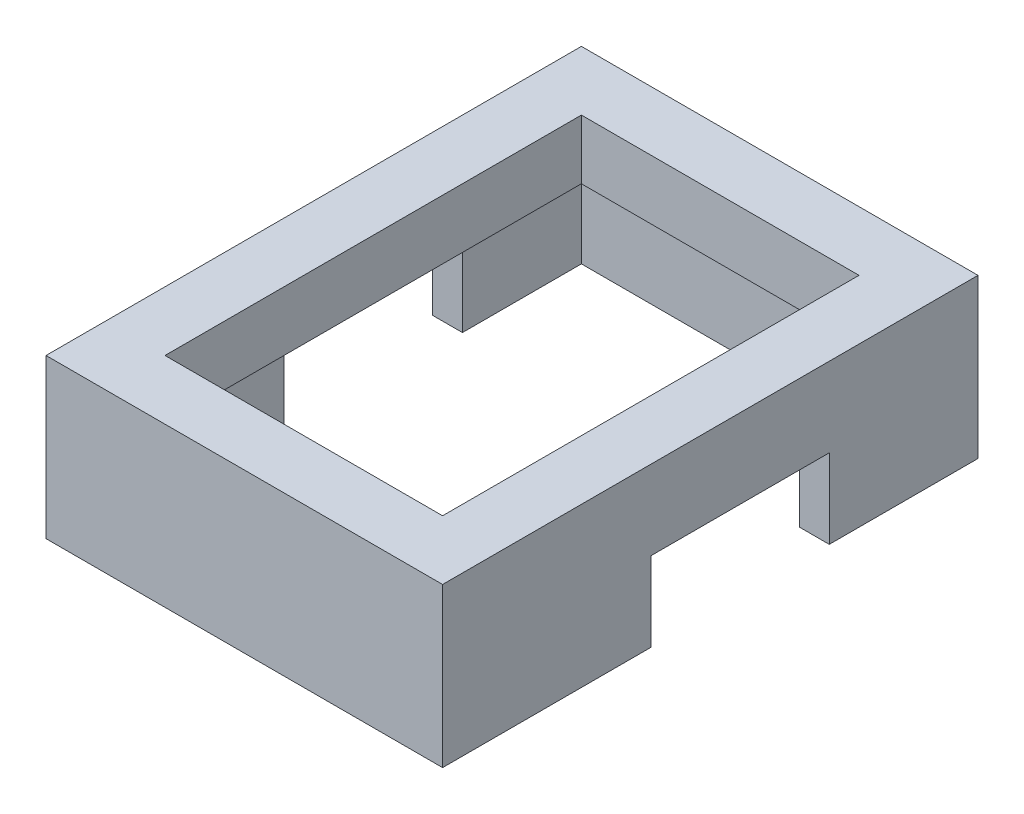
SolidWorks part; units mm, degrees
ref_plane "Front Plane" through (0, 0, 0) normal (0, 0, 1) x (1, 0, 0)
ref_plane "Top Plane" through (0, 0, 0) normal (0, 1, 0) x (1, 0, 0)
ref_plane "Right Plane" through (0, 0, 0) normal (1, 0, 0) x (0, 0, -1)
sketch "Sketch1" plane through (0, 0, 0) normal (0, 1, 0) x (1, 0, 0)
  line L1 (-20.9032, 9.871) -> (-0.9032, 9.871)
  line L2 (-20.9032, 9.871) -> (-20.9032, -17.129)
  line L3 (-20.9032, -17.129) -> (-0.9032, -17.129)
  line L4 (-0.9032, 9.871) -> (-0.9032, -17.129)
  dimension "D1" = 20
  dimension "D2" = 27
extrude "Boss-Extrude1" add sketch "Sketch1" along normal blind 8
sketch "Sketch2" plane through (-20.9032, 0, 0) normal (-1, 0, 0) x (0, 0, 1)
  line L0 (-9.871, 0) -> (17.129, 0) construction
  line L1 (-2.371, 4) -> (6.629, 4)
  line L2 (-2.371, 4) -> (-2.371, 0)
  line L3 (-2.371, 0) -> (6.629, 0)
  line L4 (6.629, 4) -> (6.629, 0)
  line L5 (-9.871, 8) -> (-9.871, 0) construction
  dimension "D1" = 9
  dimension "D2" = 4
  dimension "D3" = 7.5
extrude "Cut-Extrude1" cut sketch "Sketch2" against normal blind 20
sketch "Sketch3" plane through (0, 0, 0) normal (0, -1, 0) x (1, 0, 0)
  line L0 (-0.9032, -2.371) -> (-0.9032, -9.871) construction
  line L1 (-2.4032, -8.371) -> (-19.4032, -8.371)
  line L2 (-2.4032, -8.371) -> (-2.4032, 15.629)
  line L3 (-2.4032, 15.629) -> (-19.4032, 15.629)
  line L4 (-19.4032, -8.371) -> (-19.4032, 15.629)
  line L5 (-20.9032, -9.871) -> (-20.9032, -2.371) construction
  line L6 (-0.9032, -9.871) -> (-20.9032, -9.871) construction
  line L7 (-20.9032, 17.129) -> (-0.9032, 17.129) construction
  dimension "D1" = 1.5
  dimension "D2" = 1.5
  dimension "D3" = 1.5
  dimension "D4" = 1.5
extrude "Cut-Extrude2" cut sketch "Sketch3" against normal blind 5
sketch "Sketch4" plane through (0, 8, 0) normal (0, 1, 0) x (1, 0, 0)
  line L0 (-20.9032, 9.871) -> (-20.9032, -17.129) construction
  line L1 (-17.9032, 6.871) -> (-3.9032, 6.871)
  line L2 (-17.9032, 6.871) -> (-17.9032, -14.129)
  line L3 (-17.9032, -14.129) -> (-3.9032, -14.129)
  line L4 (-3.9032, 6.871) -> (-3.9032, -14.129)
  line L5 (-0.9032, 9.871) -> (-20.9032, 9.871) construction
  line L6 (-0.9032, -17.129) -> (-0.9032, 9.871) construction
  line L7 (-20.9032, -17.129) -> (-0.9032, -17.129) construction
  dimension "D1" = 3
  dimension "D2" = 3
  dimension "D3" = 3
  dimension "D4" = 3
extrude "Cut-Extrude3" cut sketch "Sketch4" against normal blind 7
